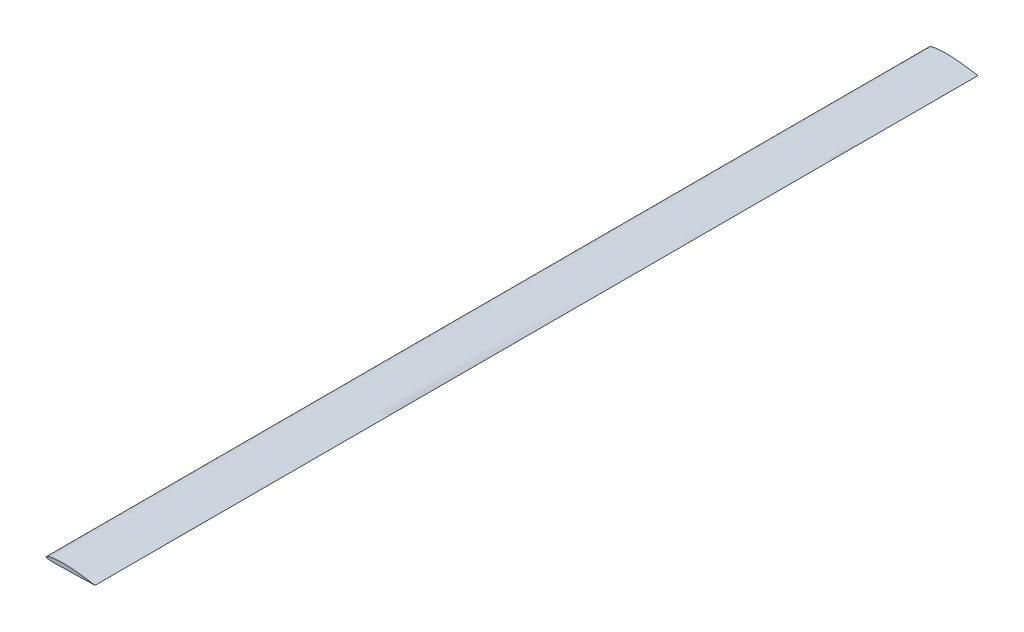
SolidWorks part; units mm, degrees
ref_plane "Front Plane" through (0, 0, 0) normal (0, 0, 1) x (1, 0, 0)
ref_plane "Top Plane" through (0, 0, 0) normal (0, 1, 0) x (1, 0, 0)
ref_plane "Right Plane" through (0, 0, 0) normal (1, 0, 0) x (0, 0, -1)
curve "Curve1"
  spline degree 3 poles (99.303, 0.018, 0) (100.1768, -0.0106, 0) (99.3044, 0.0659, 0) (98.6022, 0.1664, 0) (96.9185, 0.3889, 0) (94.883, 0.6998, 0) (92.2676, 1.1097, 0) (89.231, 1.5986, 0) (85.7846, 2.1502, 0) (81.9915, 2.742, 0) (77.8954, 3.3493, 0) (73.5406, 3.9422, 0) (68.9677, 4.4995, 0) (64.218, 5.0097, 0) (59.3372, 5.4645, 0) (54.3778, 5.8636, 0) (49.3943, 6.1992, 0) (44.4376, 6.4503, 0) (39.5569, 6.6096, 0) (34.7991, 6.6775, 0) (30.2086, 6.6419, 0) (25.8275, 6.4985, 0) (21.6951, 6.2592, 0) (17.849, 5.9192, 0) (14.3226, 5.4809, 0) (11.143, 4.9534, 0) (8.3342, 4.3478, 0) (5.9153, 3.6753, 0) (3.9009, 2.9545, 0) (2.2976, 2.2061, 0) (1.1175, 1.4622, 0) (0.4562, 0.8732, 0) (0.18, 0.4789, 0) (0.0816, 0.3044, 0) (0.0209, 0.1477, 0) (-0.0031, 0.0241, 0) (0.0017, -0.0733, 0) (0.0494, -0.1608, 0) (0.1388, -0.2609, 0) (0.2821, -0.3771, 0) (0.6288, -0.5925, 0) (1.401, -0.9072, 0) (2.7562, -1.2563, 0) (4.6749, -1.5755, 0) (7.0779, -1.8364, 0) (9.9483, -2.0308, 0) (13.2624, -2.1587, 0) (16.9912, -2.2213, 0) (21.0993, -2.224, 0) (25.5455, -2.1736, 0) (30.2829, -2.0779, 0) (35.2597, -1.9445, 0) (40.4207, -1.7811, 0) (45.7076, -1.5953, 0) (51.0606, -1.3938, 0) (56.4181, -1.185, 0) (61.7181, -0.9753, 0) (66.898, -0.7732, 0) (71.8957, -0.5848, 0) (76.65, -0.4161, 0) (81.102, -0.2717, 0) (85.1928, -0.157, 0) (88.8721, -0.0729, 0) (92.0755, -0.0183, 0) (94.798, 0.0086, 0) (96.8881, 0.0191, 0) (98.5945, 0.0084, 0) (99.303, 0.018, 0) (100.1768, -0.0106, 0) (99.3044, 0.0659, 0) knots -0.014204 -0.006419 -0.001632 0 0.001631 0.006435 0.014221 0.024766 0.037827 0.053149 0.070474 0.089536 0.110075 0.13186 0.154693 0.178371 0.20268 0.227364 0.252133 0.276728 0.300939 0.324527 0.347267 0.368992 0.389507 0.408628 0.426224 0.442179 0.456396 0.468805 0.479372 0.488086 0.494968 0.500034 0.501036 0.502094 0.502997 0.503513 0.503956 0.504409 0.504955 0.505943 0.50713 0.510998 0.518232 0.527846 0.539809 0.554056 0.57049 0.588974 0.609342 0.631393 0.654894 0.67959 0.705203 0.731447 0.75802 0.78462 0.810936 0.836657 0.861473 0.885081 0.907188 0.927507 0.945765 0.961712 0.975122 0.985796 0.993581 0.998368 1 1.001631 1.006435 1.014221 periodic
sketch "Sketch1" plane through (0, 0, 0) normal (0, 0, 1) x (1, 0, 0)
  spline S0 degree 3 poles (99.303, 0.018) (100.1768, -0.0106) (99.3044, 0.0659) (98.6022, 0.1664) (96.9185, 0.3889) (94.883, 0.6998) (92.2676, 1.1097) (89.231, 1.5986) (85.7846, 2.1502) (81.9915, 2.742) (77.8954, 3.3493) (73.5406, 3.9422) (68.9677, 4.4995) (64.218, 5.0097) (59.3372, 5.4645) (54.3778, 5.8636) (49.3943, 6.1992) (44.4376, 6.4503) (39.5569, 6.6096) (34.7991, 6.6775) (30.2086, 6.6419) (25.8275, 6.4985) (21.6951, 6.2592) (17.849, 5.9192) (14.3226, 5.4809) (11.143, 4.9534) (8.3342, 4.3478) (5.9153, 3.6753) (3.9009, 2.9545) (2.2976, 2.2061) (1.1175, 1.4622) (0.4562, 0.8732) (0.18, 0.4789) (0.0816, 0.3044) (0.0209, 0.1477) (-0.0031, 0.0241) (0.0017, -0.0733) (0.0494, -0.1608) (0.1388, -0.2609) (0.2821, -0.3771) (0.6288, -0.5925) (1.401, -0.9072) (2.7562, -1.2563) (4.6749, -1.5755) (7.0779, -1.8364) (9.9483, -2.0308) (13.2624, -2.1587) (16.9912, -2.2213) (21.0993, -2.224) (25.5455, -2.1736) (30.2829, -2.0779) (35.2597, -1.9445) (40.4207, -1.7811) (45.7076, -1.5953) (51.0606, -1.3938) (56.4181, -1.185) (61.7181, -0.9753) (66.898, -0.7732) (71.8957, -0.5848) (76.65, -0.4161) (81.102, -0.2717) (85.1928, -0.157) (88.8721, -0.0729) (92.0755, -0.0183) (94.798, 0.0086) (96.8881, 0.0191) (98.5945, 0.0084) (99.303, 0.018) (100.1768, -0.0106) (99.3044, 0.0659) knots -0.014204 -0.006419 -0.001632 0 0.001631 0.006435 0.014221 0.024766 0.037827 0.053149 0.070474 0.089536 0.110075 0.13186 0.154693 0.178371 0.20268 0.227364 0.252133 0.276728 0.300939 0.324527 0.347267 0.368992 0.389507 0.408628 0.426224 0.442179 0.456396 0.468805 0.479372 0.488086 0.494968 0.500034 0.501036 0.502094 0.502997 0.503513 0.503956 0.504409 0.504955 0.505943 0.50713 0.510998 0.518232 0.527846 0.539809 0.554056 0.57049 0.588974 0.609342 0.631393 0.654894 0.67959 0.705203 0.731447 0.75802 0.78462 0.810936 0.836657 0.861473 0.885081 0.907188 0.927507 0.945765 0.961712 0.975122 0.985796 0.993581 0.998368 1 1.001631 1.006435 1.014221 only from (100, 0) to (100, 0) construction
  spline S1 degree 3 poles (99.303, 0.018) (100.1768, -0.0106) (99.3044, 0.0659) (98.6022, 0.1664) (96.9185, 0.3889) (94.883, 0.6998) (92.2676, 1.1097) (89.231, 1.5986) (85.7846, 2.1502) (81.9915, 2.742) (77.8954, 3.3493) (73.5406, 3.9422) (68.9677, 4.4995) (64.218, 5.0097) (59.3372, 5.4645) (54.3778, 5.8636) (49.3943, 6.1992) (44.4376, 6.4503) (39.5569, 6.6096) (34.7991, 6.6775) (30.2086, 6.6419) (25.8275, 6.4985) (21.6951, 6.2592) (17.849, 5.9192) (14.3226, 5.4809) (11.143, 4.9534) (8.3342, 4.3478) (5.9153, 3.6753) (3.9009, 2.9545) (2.2976, 2.2061) (1.1175, 1.4622) (0.4562, 0.8732) (0.18, 0.4789) (0.0816, 0.3044) (0.0209, 0.1477) (-0.0031, 0.0241) (0.0017, -0.0733) (0.0494, -0.1608) (0.1388, -0.2609) (0.2821, -0.3771) (0.6288, -0.5925) (1.401, -0.9072) (2.7562, -1.2563) (4.6749, -1.5755) (7.0779, -1.8364) (9.9483, -2.0308) (13.2624, -2.1587) (16.9912, -2.2213) (21.0993, -2.224) (25.5455, -2.1736) (30.2829, -2.0779) (35.2597, -1.9445) (40.4207, -1.7811) (45.7076, -1.5953) (51.0606, -1.3938) (56.4181, -1.185) (61.7181, -0.9753) (66.898, -0.7732) (71.8957, -0.5848) (76.65, -0.4161) (81.102, -0.2717) (85.1928, -0.157) (88.8721, -0.0729) (92.0755, -0.0183) (94.798, 0.0086) (96.8881, 0.0191) (98.5945, 0.0084) (99.303, 0.018) (100.1768, -0.0106) (99.3044, 0.0659) knots -0.014204 -0.006419 -0.001632 0 0.001631 0.006435 0.014221 0.024766 0.037827 0.053149 0.070474 0.089536 0.110075 0.13186 0.154693 0.178371 0.20268 0.227364 0.252133 0.276728 0.300939 0.324527 0.347267 0.368992 0.389507 0.408628 0.426224 0.442179 0.456396 0.468805 0.479372 0.488086 0.494968 0.500034 0.501036 0.502094 0.502997 0.503513 0.503956 0.504409 0.504955 0.505943 0.50713 0.510998 0.518232 0.527846 0.539809 0.554056 0.57049 0.588974 0.609342 0.631393 0.654894 0.67959 0.705203 0.731447 0.75802 0.78462 0.810936 0.836657 0.861473 0.885081 0.907188 0.927507 0.945765 0.961712 0.975122 0.985796 0.993581 0.998368 1 1.001631 1.006435 1.014221 only from (100, 0) to (100, 0)
extrude "Boss-Extrude1" add sketch "Sketch1" along normal blind 1800
